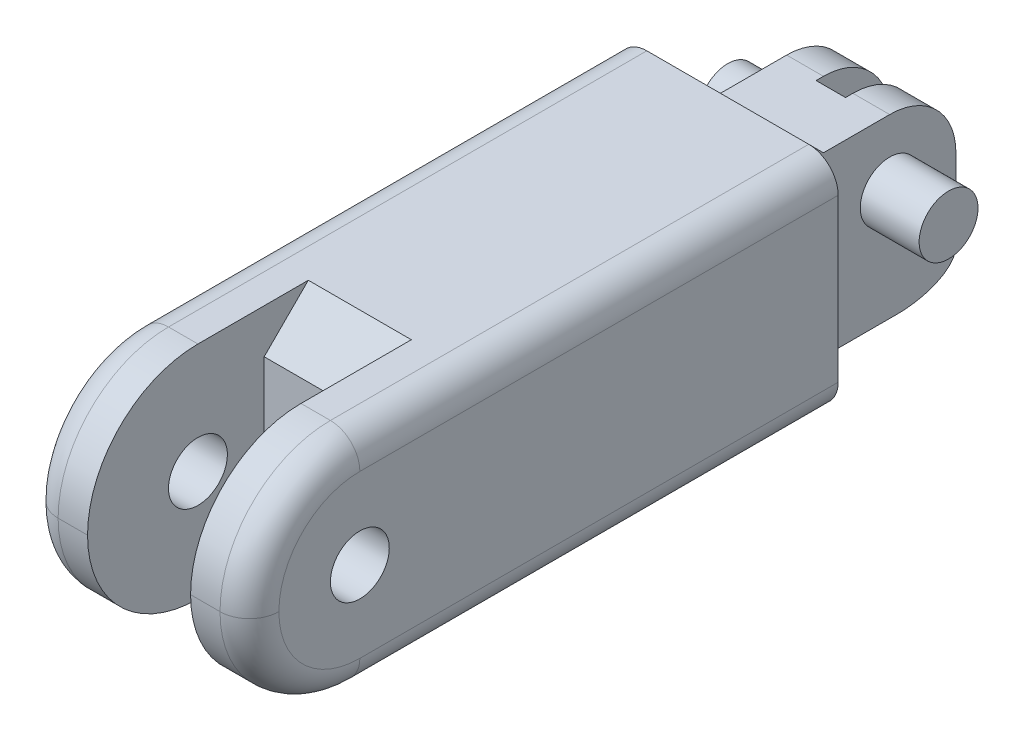
SolidWorks part; units mm, degrees
ref_plane "Front Plane" through (0, 0, 0) normal (0, 0, 1) x (1, 0, 0)
ref_plane "Top Plane" through (0, 0, 0) normal (0, 1, 0) x (1, 0, 0)
ref_plane "Right Plane" through (0, 0, 0) normal (1, 0, 0) x (0, 0, -1)
sketch "Sketch1" plane through (0, 0, 0) normal (0, 0, 1) x (1, 0, 0)
  line L1 (-7.5, 7.5) -> (7.5, 7.5)
  line L2 (-7.5, 7.5) -> (-7.5, -7.5)
  line L3 (-7.5, -7.5) -> (7.5, -7.5)
  line L4 (7.5, 7.5) -> (7.5, -7.5)
  line L5 (-7.5, 7.5) -> (7.5, -7.5) construction
  line L6 (-7.5, -7.5) -> (7.5, 7.5) construction
  point P0 (0, 0)
  dimension "D1" = 15
  dimension "D2" = 15
extrude "Boss-Extrude1" add sketch "Sketch1" along normal blind 55 contours L2 L1 L4 L3
sketch "Sketch3" plane through (0, 0, 55) normal (0, 0, 1) x (1, 0, 0)
  line L0 (-7.5, -7.5) -> (7.5, -7.5) construction
  line L1 (-3.5, 7.5) -> (3.5, 7.5)
  line L2 (-3.5, 7.5) -> (-3.5, -7.5)
  line L3 (-3.5, -7.5) -> (3.5, -7.5)
  line L4 (3.5, 7.5) -> (3.5, -7.5)
  line L5 (-3.5, 7.5) -> (3.5, -7.5) construction
  line L6 (-3.5, -7.5) -> (3.5, 7.5) construction
  point P0 (0, 0)
  dimension "D1" = 7
extrude "Cut-Extrude1" cut sketch "Sketch3" against normal blind 12
sketch "Sketch4" plane through (7.5, 0, 0) normal (1, 0, 0) x (0, 0, -1)
  line L0 (-38.6919, 0) -> (3.3242, 0) construction
  line L1 (-55, 7.5) -> (-55, -7.5) construction
  circle A0 centre (-47.5, 0) radius 2
  dimension "D2" = 4
  dimension "D1" = 7.5
extrude "Cut-Extrude2" cut sketch "Sketch4" against normal blind 15
sketch "Sketch5" plane through (0, 0, 0) normal (0, 0, -1) x (-1, 0, 0)
  line L0 (7.5, -7.5) -> (-7.5, -7.5) construction
  line L1 (-7.5, 7.5) -> (-3.5, 7.5)
  line L2 (-7.5, 7.5) -> (-7.5, -7.5)
  line L3 (-7.5, -7.5) -> (-3.5, -7.5)
  line L4 (-3.5, 7.5) -> (-3.5, -7.5)
  line L5 (-7.5, 7.5) -> (-3.5, -7.5) construction
  line L6 (-7.5, -7.5) -> (-3.5, 7.5) construction
  line L8 (3.5, 7.5) -> (7.5, 7.5)
  line L9 (3.5, 7.5) -> (3.5, -7.5)
  line L10 (3.5, -7.5) -> (7.5, -7.5)
  line L11 (7.5, 7.5) -> (7.5, -7.5)
  line L12 (3.5, 7.5) -> (7.5, -7.5) construction
  line L13 (3.5, -7.5) -> (7.5, 7.5) construction
  point P0 (-5.5, 0)
  point P7 (5.5, 0)
  dimension "D1" = 4
  dimension "D2" = 4
  dimension "D3" = 3.5
  dimension "D4" = 3.5
extrude "Cut-Extrude3" cut sketch "Sketch5" against normal blind 15
sketch "Sketch6" plane through (0, 0, 0) normal (1, 0, 0) x (0, 0, -1)
  circle A0 centre (-7.5, 0) radius 2
  dimension "D1" = 7.5
extrude "Boss-Extrude2" add sketch "Sketch6" along normal blind 7.5 and the other way blind 7.5
fillet "Fillet1" radius 7.5 4 edges at (5.5, -7.5, 55) (-5.5, -7.5, 55) (-5.5, 7.5, 55) (5.5, 7.5, 55)
sketch "Sketch7" plane through (0, 0, 0) normal (1, 0, 0) x (0, 0, -1)
  line L0 (-39.1207, 0) -> (4.4951, 0) construction
  line L7 (0, -7.5) -> (0, 7.5) construction
  line L17 (-43, 7.5) -> (-43, 4.5)
  line L18 (-43, 4.5) -> (-40, 7.5)
  line L19 (-47.5, 7.5) -> (-15, 7.5) construction
  line L20 (-40, 7.5) -> (-43, 7.5)
  dimension "D4" = 3
  dimension "D5" = 40
extrude "Cut-Extrude6" cut sketch "Sketch7" against normal blind 3.5 and the other way blind 3.5
fillet "Fillet2" radius 2 8 edges at (-7.5, -7.5, 31.25) (-7.5, -5.3033, 52.8033) (-7.5, 5.3033, 52.8033) (7.5, -7.5, 31.25) (7.5, -5.3033, 52.8033) (7.5, 5.3033, 52.8033) (-7.5, 7.5, 31.25) (7.5, 7.5, 31.25)
sketch "Sketch8" plane through (0, 0, 0) normal (1, 0, 0) x (0, 0, -1)
  line L0 (-15, 7.5) -> (-12, 4.5)
  line L1 (-12, 4.5) -> (-7.5, 4.5)
  line L2 (-15, 7.5) -> (0, 7.5) construction
  line L3 (-7.5, 0) -> (-7.5, 14.3736) construction
  line L7 (0, -7.5) -> (0, 7.5)
  line L8 (0, 7.5) -> (-15, 7.5)
  line L9 (-3, 0) -> (-3, -7.5)
  line L10 (-15, -7.5) -> (0, -7.5) construction
  line L11 (-3, -7.5) -> (0, -7.5)
  arc A1 (-7.5, 4.5) -> (-3, 0) centre (-7.5, 0) cw
  dimension "D1" = 3
  dimension "D2" = 45
extrude "Cut-Extrude7" cut sketch "Sketch8" against normal blind 7.5 and the other way blind 7.5
fillet "Fillet3" radius 4 1 edges at (0, -7.5, 3) second distance 2 first distance on face at (0, -7.5, 28.5)
sketch "Sketch9" plane through (0, 0, 0) normal (1, 0, 0) x (0, 0, -1)
  line L0 (-13.9466, 0) -> (1.0526, 0) construction
  line L1 (-7.5, 0) -> (-7.5, 8.6585) construction
  line L2 (-8, -0.5) -> (-8, 9.1476)
  line L3 (-8, -0.5) -> (1.6476, -0.5)
  arc A0 (-8, 9.1476) -> (1.6476, -0.5) centre (-8, -0.5) cw
  dimension "D1" = 0.5
  dimension "D2" = 0.5
extrude "Cut-Extrude8" cut sketch "Sketch9" against normal blind 1 and the other way blind 1
